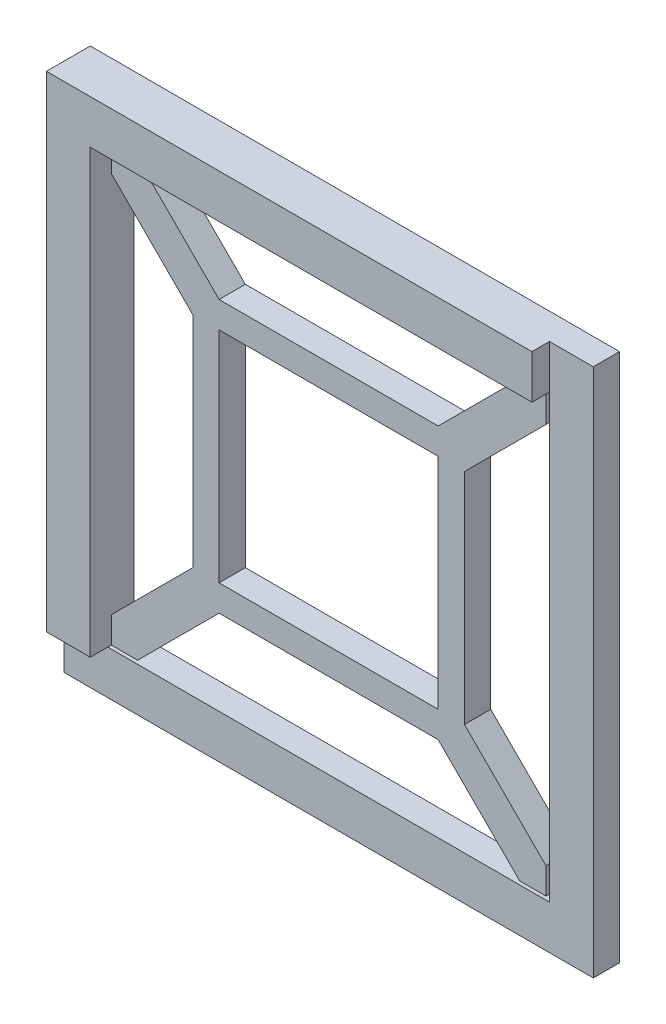
SolidWorks part; units mm, degrees
ref_plane "Front Plane" through (0, 0, 0) normal (0, 0, 1) x (1, 0, 0)
ref_plane "Top Plane" through (0, 0, 0) normal (0, 1, 0) x (1, 0, 0)
ref_plane "Right Plane" through (0, 0, 0) normal (1, 0, 0) x (0, 0, -1)
sketch "Sketch1" plane through (0, 0, 0) normal (0, 0, 1) x (1, 0, 0)
  line L0 (-25.2, 25.2) -> (25.2, 25.2)
  line L1 (-24.8, 24.8) -> (24.8, 24.8)
  line L2 (-24.8, 24.8) -> (-24.8, -24.8)
  line L3 (-24.8, -24.8) -> (24.8, -24.8)
  line L4 (24.8, 24.8) -> (24.8, -24.8)
  line L5 (-24.8, 24.8) -> (24.8, -24.8) construction
  line L6 (-24.8, -24.8) -> (24.8, 24.8) construction
  line L7 (25.2, 25.2) -> (25.2, -25.2)
  line L8 (-25.2, -25.2) -> (25.2, -25.2)
  line L9 (-25.2, 25.2) -> (-25.2, -25.2)
  line L10 (21.8, 24.8) -> (9.5, 12.5)
  line L11 (24.8, 21.8) -> (12.5, 9.5)
  line L12 (24.8, -21.8) -> (12.5, -9.5)
  line L13 (-12.5, -12.5) -> (12.5, -12.5)
  line L14 (-12.5, -12.5) -> (-12.5, 12.5)
  line L15 (-12.5, 12.5) -> (12.5, 12.5)
  line L16 (12.5, -12.5) -> (12.5, 12.5)
  line L17 (-12.5, -12.5) -> (12.5, 12.5) construction
  line L18 (-12.5, 12.5) -> (12.5, -12.5) construction
  line L19 (21.8, -24.8) -> (9.5, -12.5)
  line L20 (-21.8, -24.8) -> (-9.5, -12.5)
  line L21 (-24.8, -21.8) -> (-12.5, -9.5)
  line L22 (-24.8, 21.8) -> (-12.5, 9.5)
  line L23 (-21.8, 24.8) -> (-9.5, 12.5)
  point P0 (0, 0)
  point P14 (0, 0)
  point P34 (0, 0)
  dimension "D1" = 49.6
  dimension "D3" = 3
  dimension "D4" = 3
  dimension "D5" = 25
  dimension "D2" = 0.4
extrude "Extrude-Thin1" add sketch "Sketch1" along normal blind 3 thin contours L0 L7 L8 L9 thin type one direction wall 5
extrude "Boss-Extrude1" add sketch "Sketch1<4>" along normal blind 3 separate body contours L19 L3 L4 L12 L16 L13 | L21 L2 L3 L20 L13 L14 | L23 L1 L2 L22 L14 L15 | L16 L11 L4 L1 L10 L15 region at (-17.9, 17.9, 0) region at (17.9, 17.9, 0) region at (-17.9, -17.9, 0) region at (17.9, -17.9, 0)
sketch "Sketch1<4>" plane through (0, 0, 0) normal (0, 0, 1) x (1, 0, 0) same geometry as "Sketch1"
extrude "Extrude-Thin2" add sketch "Sketch1<5>" along normal blind 3 thin contours L13 L16 L15 L14 thin type one direction wall 3
sketch "Sketch1<5>" plane through (0, 0, 0) normal (0, 0, 1) x (1, 0, 0) same geometry as "Sketch1"
sketch "Sketch2" plane through (0, 0, 3) normal (0, 0, 1) x (1, 0, 0)
  line L0 (-25.2, 25.2) -> (25.2, 25.2) construction
  line L1 (-25.2, 25.2) -> (-25.2, -25.2) construction
  line L2 (-25.2, 25.2) -> (25.2, 25.2)
  line L3 (-25.2, 25.2) -> (-25.2, -25.2)
extrude "Extrude-Thin3" add sketch "Sketch2" along normal blind 2 thin thin type one direction wall 5
